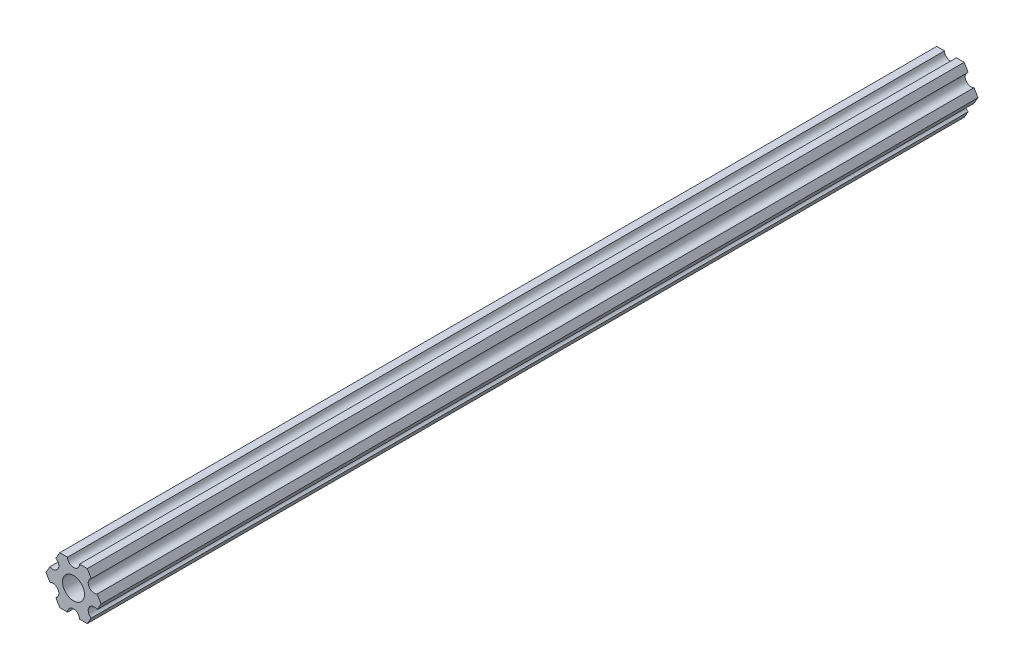
SolidWorks part; units mm, degrees
material "6061-T6 (SS)"
ref_plane "Front Plane" through (0, 0, 0) normal (0, 0, 1) x (1, 0, 0)
ref_plane "Top Plane" through (0, 0, 0) normal (0, 1, 0) x (1, 0, 0)
ref_plane "Right Plane" through (0, 0, 0) normal (1, 0, 0) x (0, 0, -1)
sketch "Sketch1" plane through (0, 0, 0) normal (0, 0, 1) x (1, 0, 0)
  line L0 (-4.7055, -4.5498) -> (-3.6662, -6.35)
  line L1 (-3.6662, -6.35) -> (-1.5875, -6.35)
  line L2 (1.5875, -6.35) -> (3.6662, -6.35)
  line L3 (3.6662, -6.35) -> (4.7055, -4.5498)
  line L4 (6.293, -1.8002) -> (7.3323, 0)
  line L5 (7.3323, 0) -> (6.293, 1.8002)
  line L6 (4.7055, 4.5498) -> (3.6662, 6.35)
  line L7 (3.6662, 6.35) -> (1.5875, 6.35)
  line L8 (-1.5875, 6.35) -> (-3.6662, 6.35)
  line L9 (-3.6662, 6.35) -> (-4.7055, 4.5498)
  line L10 (-6.293, 1.8002) -> (-7.3323, 0)
  line L11 (-7.3323, 0) -> (-6.293, -1.8002)
  circle A0 centre (0, 0) radius 2.9337
  arc A1 (-6.293, -1.8002) -> (-4.7055, -4.5498) centre (-5.4993, -3.175) cw
  arc A2 (-1.5875, -6.35) -> (1.5875, -6.35) centre (0, -6.35) cw
  arc A3 (4.7055, -4.5498) -> (6.293, -1.8002) centre (5.4993, -3.175) cw
  arc A4 (6.293, 1.8002) -> (4.7055, 4.5498) centre (5.4993, 3.175) cw
  arc A5 (1.5875, 6.35) -> (-1.5875, 6.35) centre (0, 6.35) cw
  arc A6 (-4.7055, 4.5498) -> (-6.293, 1.8002) centre (-5.4993, 3.175) cw
extrude "Boss-Extrude1" add sketch "Sketch1" against normal blind 233.6165
